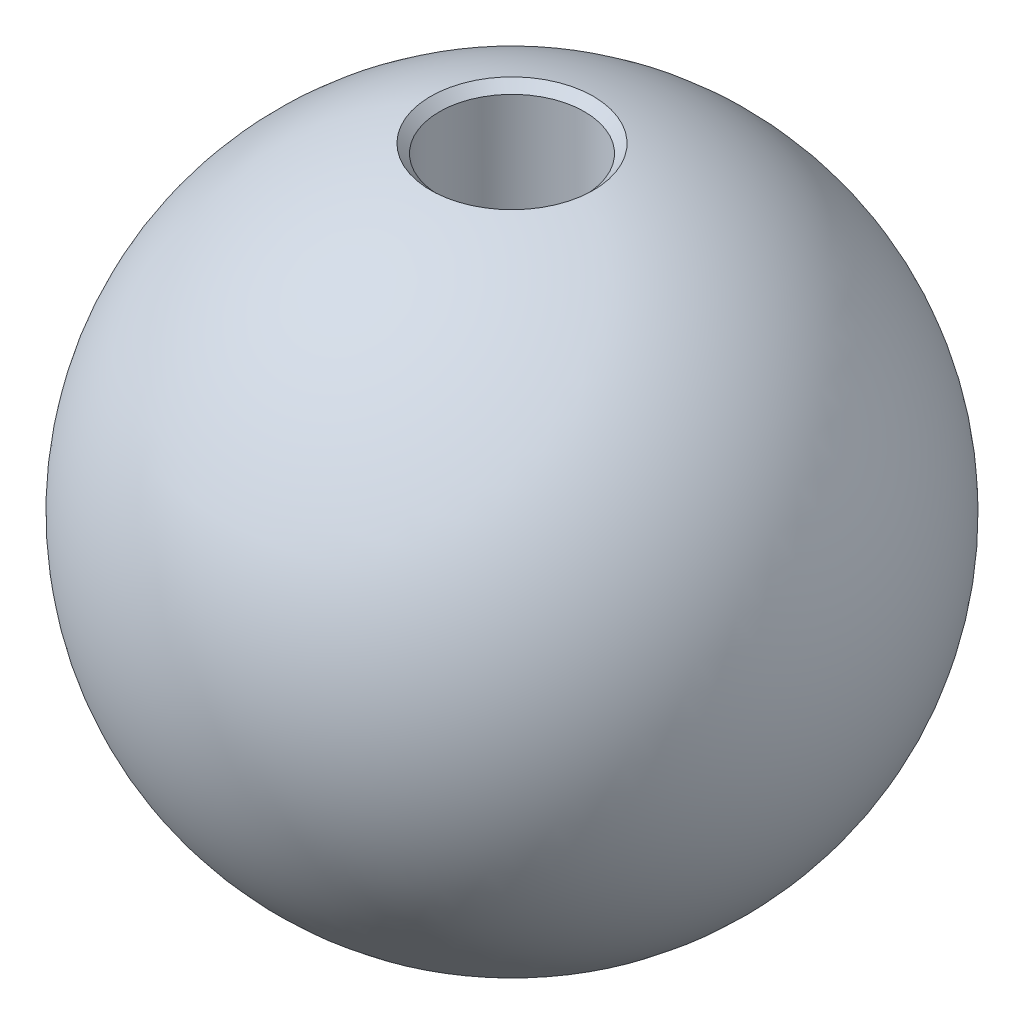
SolidWorks part; units mm, degrees
ref_plane "Front Plane" through (0, 0, 0) normal (0, 0, 1) x (1, 0, 0)
ref_plane "Top Plane" through (0, 0, 0) normal (0, 1, 0) x (1, 0, 0)
ref_plane "Right Plane" through (0, 0, 0) normal (1, 0, 0) x (0, 0, -1)
sketch "Sketch1" plane through (0, 0, 0) normal (0, 0, 1) x (1, 0, 0)
  line L0 (-7.5, 0) -> (7.5, 0) construction
  point P4 (0, 0)
  dimension "Diameter" = 15
sketch "Sketch2" plane through (0, 0, 0) normal (0, 0, 1) x (1, 0, 0)
  line L0 (-7.5, 0) -> (7.5, 0)
  arc A1 (7.5, 0) -> (-7.5, 0) centre (0, 0) ccw
revolve "Revolve1" add sketch "Sketch2" angle 360 about L0
ref_plane "Plane1" through (0, 7.5, 0) normal (0, 1, 0) x (1, 0, 0)
hole_wizard "Tap Drill for M4x0.7 Tap2" positions "Sketch3" profile "Sketch4" hole size "M4x0.7" standard "ANSI Metric"
sketch "Sketch3" plane through (0, 7.5, 0) normal (0, 1, 0) x (1, 0, 0)
  point P0 (0, 0)
sketch "Sketch4" plane through (0, 7.5, 0) normal (1, 0, 0) x (0, 0, 1)
  line L0 (0, 0) -> (0, 6.9914)
  line L1 (0, 6.9914) -> (1.65, 6)
  line L2 (1.65, 6) -> (1.65, 0)
  line L5 (1.65, 0) -> (0, 0)
  line L10 (0, 6.9914) -> (-1.65, 6) construction
  line L11 (0, -6.35) -> (0, 107.95) construction
  dimension "Hole Dia." = 3.3
  dimension "Hole Depth" = 6
  dimension "Drill Angle" = 118
chamfer "Chamfer1" distance 0.25 angle 45 1 edges at (0, 7.3162, -1.65) first distance on face at (0, 1.5, 1.65)
